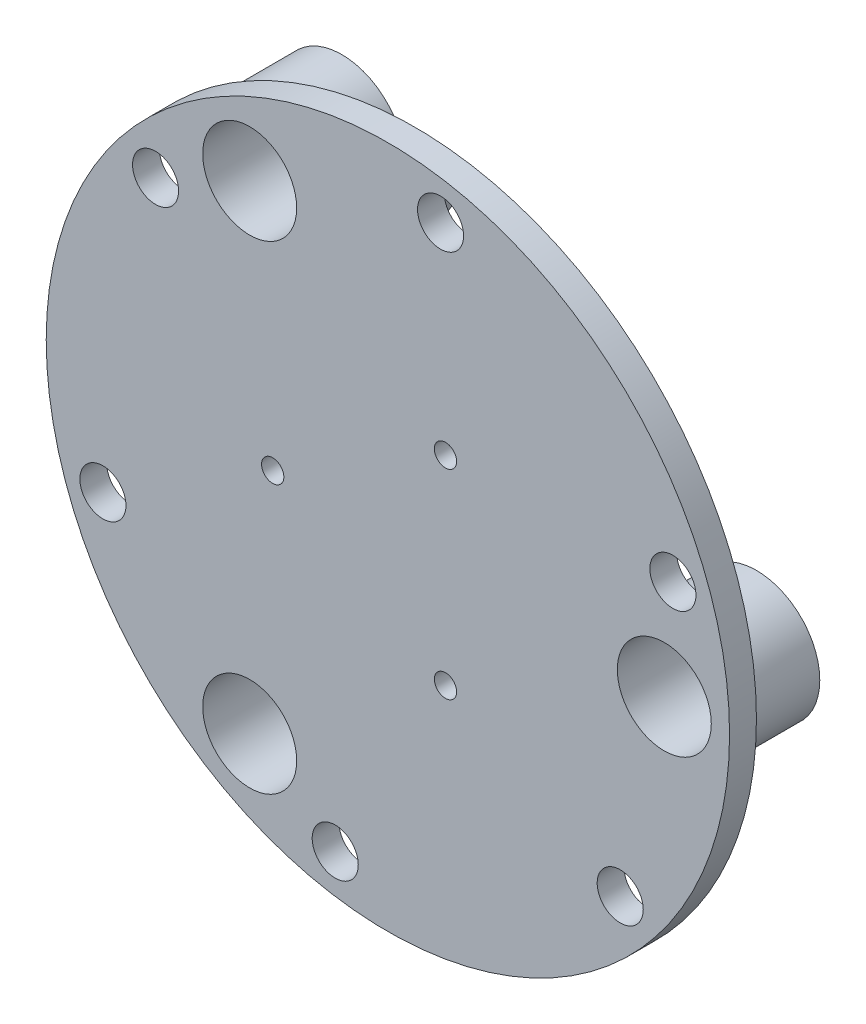
SolidWorks part; units mm, degrees
ref_plane "Front Plane" through (0, 0, 0) normal (0, 0, 1) x (1, 0, 0)
ref_plane "Top Plane" through (0, 0, 0) normal (0, 1, 0) x (1, 0, 0)
ref_plane "Right Plane" through (0, 0, 0) normal (1, 0, 0) x (0, 0, -1)
sketch "S01 - Joining centre of floating Y" plane through (0, 0, 0) normal (0, 0, 1) x (1, 0, 0)
  circle A0 centre (0, 0) radius 9
  dimension "D1" = 18
extrude "01 - Joining centre of floating Y" add sketch "S01 - Joining centre of floating Y" along normal blind 3.5 from offset 33.5
sketch "S02 - Floating spoke 1" plane through (0, 0, 0) normal (0, 0, 1) x (1, 0, 0)
  line L0 (4.65, -8.054) -> (-21.3308, -23.054)
  line L1 (-30.6308, -6.946) -> (-4.65, 8.054)
  arc A0 (-21.3308, -23.054) -> (-30.6308, -6.946) centre (-25.9808, -15) cw
  arc A1 (-4.65, 8.054) -> (4.65, -8.054) centre (0, 0) cw
  dimension "D1" = 9.3
  dimension "D2" = 9.3
  dimension "D3" = 4.65
  dimension "D4" = 4.65
  dimension "D5" = 21.3308
  dimension "D6" = 25.9808
  dimension "D7" = 30.6308
  dimension "D8" = 6.946
extrude "02 - Floating spoke 1" add sketch "S02 - Floating spoke 1" along normal blind 3.5 from offset 33.5
sketch "S03 - Floating spoke 2" plane through (0, 0, 0) normal (0, 0, 1) x (1, 0, 0)
  line L0 (4.65, 8.054) -> (30.6308, -6.946)
  line L1 (21.3308, -23.054) -> (-4.65, -8.054)
  arc A0 (30.6308, -6.946) -> (21.3308, -23.054) centre (25.9808, -15) cw
  arc A1 (-4.65, -8.054) -> (4.65, 8.054) centre (0, 0) cw
  dimension "D1" = 9.3
  dimension "D2" = 9.3
  dimension "D3" = 4.65
  dimension "D4" = 21.3308
  dimension "D5" = 25.9808
  dimension "D6" = 30.6308
  dimension "D7" = 4.65
  dimension "D8" = 6.946
extrude "03 - Floating spoke 2" add sketch "S03 - Floating spoke 2" along normal blind 3.5 from offset 33.5
sketch "S04 - Floating spoke 3" plane through (0, 0, 0) normal (0, 0, 1) x (1, 0, 0)
  line L0 (-9.3, 0) -> (-9.3, 30)
  line L1 (9.3, 30) -> (9.3, 0)
  arc A0 (-9.3, 30) -> (9.3, 30) centre (0, 30) cw
  arc A1 (9.3, 0) -> (-9.3, 0) centre (0, 0) cw
  dimension "D1" = 9.3
  dimension "D2" = 30
extrude "04 - Floating spoke 3" add sketch "S04 - Floating spoke 3" along normal blind 3.5 from offset 33.5
sketch "S05 - Moving tendon tie web 1" plane through (0, 0, 0) normal (0, 0, 1) x (1, 0, 0)
  line L0 (25.2997, -21.2631) -> (6.8189, -19.2535)
  line L1 (8.1811, -6.7273) -> (26.6618, -8.7369)
  arc A0 (6.8189, -19.2535) -> (8.1811, -6.7273) centre (7.5, -12.9904) cw
  arc A1 (26.6618, -8.7369) -> (25.2997, -21.2631) centre (25.9808, -15) cw
  dimension "D1" = 6.3
  dimension "D2" = 6.3
  dimension "D3" = 6.8189
  dimension "D4" = 7.5
  dimension "D5" = 8.1811
  dimension "D6" = 25.2997
  dimension "D7" = 25.9808
  dimension "D8" = 26.6618
  dimension "D9" = 6.7273
  dimension "D10" = 8.7369
extrude "05 - Moving tendon tie web 1" add sketch "S05 - Moving tendon tie web 1" along normal blind 3.5 from offset 33.5
sketch "S06 - Tendon anchor base 1" plane through (0, 0, 0) normal (0, 0, 1) x (1, 0, 0)
  circle A0 centre (7.5, -12.9904) radius 4.2
  dimension "D1" = 8.4
  dimension "D2" = 7.5
  dimension "D3" = 12.9904
extrude "06 - Tendon anchor base 1" add sketch "S06 - Tendon anchor base 1" along normal blind 3.7 from offset 29.8
sketch "S07 - Tendon mouth 1" plane through (0, 0, 0) normal (0, 0, 1) x (1, 0, 0)
  circle A0 centre (7.5, -12.9904) radius 3.15
  dimension "D1" = 6.3
  dimension "D2" = 7.5
  dimension "D3" = 12.9904
extrude "07 - Tendon mouth 1" add sketch "S07 - Tendon mouth 1" along normal blind 1.8 from offset 28
sketch "S08 - Moving tendon tie web 2" plane through (0, 0, 0) normal (0, 0, 1) x (1, 0, 0)
  line L0 (5.7645, 32.5417) -> (13.2645, 15.5321)
  line L1 (1.7355, 10.4487) -> (-5.7645, 27.4583)
  arc A0 (13.2645, 15.5321) -> (1.7355, 10.4487) centre (7.5, 12.9904) cw
  arc A1 (-5.7645, 27.4583) -> (5.7645, 32.5417) centre (0, 30) cw
  dimension "D1" = 6.3
  dimension "D2" = 6.3
  dimension "D3" = 1.7355
  dimension "D4" = 5.7645
  dimension "D5" = 7.5
  dimension "D6" = 13.2645
  dimension "D7" = 5.7645
  dimension "D8" = 10.4487
  dimension "D9" = 27.4583
extrude "08 - Moving tendon tie web 2" add sketch "S08 - Moving tendon tie web 2" along normal blind 3.5 from offset 33.5
sketch "S09 - Tendon anchor base 2" plane through (0, 0, 0) normal (0, 0, 1) x (1, 0, 0)
  circle A0 centre (7.5, 12.9904) radius 4.2
  dimension "D1" = 8.4
  dimension "D2" = 7.5
  dimension "D3" = 12.9904
extrude "09 - Tendon anchor base 2" add sketch "S09 - Tendon anchor base 2" along normal blind 3.7 from offset 29.8
sketch "S10 - Tendon mouth 2" plane through (0, 0, 0) normal (0, 0, 1) x (1, 0, 0)
  circle A0 centre (7.5, 12.9904) radius 3.15
  dimension "D1" = 6.3
  dimension "D2" = 7.5
  dimension "D3" = 12.9904
extrude "10 - Tendon mouth 2" add sketch "S10 - Tendon mouth 2" along normal blind 1.8 from offset 28
sketch "S11 - Moving tendon tie web 3" plane through (0, 0, 0) normal (0, 0, 1) x (1, 0, 0)
  line L0 (-31.0642, -11.2786) -> (-20.0835, 3.7214)
  line L1 (-9.9165, -3.7214) -> (-20.8973, -18.7214)
  arc A0 (-20.0835, 3.7214) -> (-9.9165, -3.7214) centre (-15, 0) cw
  arc A1 (-20.8973, -18.7214) -> (-31.0642, -11.2786) centre (-25.9808, -15) cw
  dimension "D1" = 6.3
  dimension "D2" = 6.3
  dimension "D3" = 9.9165
  dimension "D4" = 15
  dimension "D5" = 20.0835
  dimension "D6" = 20.8973
  dimension "D7" = 25.9808
  dimension "D8" = 31.0642
  dimension "D9" = 11.2786
extrude "11 - Moving tendon tie web 3" add sketch "S11 - Moving tendon tie web 3" along normal blind 3.5 from offset 33.5
sketch "S12 - Tendon anchor base 3" plane through (0, 0, 0) normal (0, 0, 1) x (1, 0, 0)
  circle A0 centre (-15, 0) radius 4.2
  dimension "D1" = 8.4
  dimension "D2" = 15
extrude "12 - Tendon anchor base 3" add sketch "S12 - Tendon anchor base 3" along normal blind 3.7 from offset 29.8
sketch "S13 - Tendon mouth 3" plane through (0, 0, 0) normal (0, 0, 1) x (1, 0, 0)
  circle A0 centre (-15, 0) radius 3.15
  dimension "D1" = 6.3
  dimension "D2" = 15
extrude "13 - Tendon mouth 3" add sketch "S13 - Tendon mouth 3" along normal blind 1.8 from offset 28
sketch "S14 - Joined drive hoop" plane through (0, 0, 0) normal (0, 0, 1) x (1, 0, 0)
  circle A0 centre (0, 0) radius 44.5
  dimension "D2" = 89
extrude "14 - Joined drive hoop" add sketch "S14 - Joined drive hoop" along normal blind 3.5 from offset 33.5
sketch "S15 - Sliding guide barrel 1" plane through (0, 0, 0) normal (0, 0, 1) x (1, 0, 0)
  circle A0 centre (36, 0) radius 8.25
  dimension "D1" = 16.5
  dimension "D2" = 36
extrude "15 - Sliding guide barrel 1" add sketch "S15 - Sliding guide barrel 1" along normal blind 12 from offset 25
sketch "S16 - Sliding guide barrel 2" plane through (0, 0, 0) normal (0, 0, 1) x (1, 0, 0)
  circle A0 centre (-18, 31.1769) radius 8.25
  dimension "D1" = 16.5
  dimension "D2" = 18
  dimension "D3" = 31.1769
extrude "16 - Sliding guide barrel 2" add sketch "S16 - Sliding guide barrel 2" along normal blind 12 from offset 25
sketch "S17 - Sliding guide barrel 3" plane through (0, 0, 0) normal (0, 0, 1) x (1, 0, 0)
  circle A0 centre (-18, -31.1769) radius 8.25
  dimension "D1" = 16.5
  dimension "D2" = 18
  dimension "D3" = 31.1769
extrude "17 - Sliding guide barrel 3" add sketch "S17 - Sliding guide barrel 3" along normal blind 12 from offset 25
sketch "S18 - Guide bushing seats" plane through (0, 0, 0) normal (0, 0, 1) x (1, 0, 0)
  circle A0 centre (36, 0) radius 6.12
  circle A1 centre (-18, 31.1769) radius 6.12
  circle A2 centre (-18, -31.1769) radius 6.12
  dimension "D1" = 12.24
  dimension "D2" = 12.24
  dimension "D3" = 12.24
  dimension "D4" = 36
  dimension "D5" = 18
  dimension "D6" = 31.1769
  dimension "D7" = 31.1769
extrude "18 - Guide bushing seats" cut sketch "S18 - Guide bushing seats" along normal blind 14 from offset 24
sketch "S19 - Through tendon tie eyes" plane through (0, 0, 0) normal (0, 0, 1) x (1, 0, 0)
  circle A0 centre (7.5, -12.9904) radius 1.45
  circle A1 centre (7.5, 12.9904) radius 1.45
  circle A2 centre (-15, 0) radius 1.45
  dimension "D1" = 2.9
  dimension "D2" = 2.9
  dimension "D3" = 2.9
  dimension "D4" = 7.5
  dimension "D5" = 15
  dimension "D6" = 12.9904
  dimension "D7" = 12.9904
extrude "19 - Through tendon tie eyes" cut sketch "S19 - Through tendon tie eyes" along normal blind 10 from offset 27.8
sketch3d "Plane points - Integral B1 fork cheek L"
  point P0 (-25.9808, -15, 28)
  point P1 (-8.5941, -10.3413, 28)
  point P2 (-25.9808, -15, 10)
ref_plane "Drilling plane - Integral B1 fork cheek L" through (2.0096, -7.5, 0) normal (-0.2588, 0.9659, 0) x (0.9659, 0.2588, 0)
sketch "S20 - Integral B1 fork cheek L" plane through (2.0096, -7.5, 0) normal (-0.2588, 0.9659, 0) x (0.9659, 0.2588, 0)
  line L0 (-35.0778, -34.5) -> (-22.8778, -34.5)
  line L1 (-22.8778, -34.5) -> (-24.0278, -28)
  line L2 (-33.9278, -28) -> (-35.0778, -34.5)
  arc A0 (-24.0278, -28) -> (-33.9278, -28) centre (-28.9778, -28) ccw
  dimension "D1" = 4.95
  dimension "D2" = 22.8778
  dimension "D3" = 28.9778
  dimension "D4" = 35.0778
  dimension "D5" = 28
  dimension "D6" = 34.5
extrude "20 - Integral B1 fork cheek L" add sketch "S20 - Integral B1 fork cheek L" along normal blind 3.6 from offset 7.2 offset against normal yes
sketch3d "Plane points - Integral B1 fork cheek R"
  point P0 (-25.9808, -15, 28)
  point P1 (-8.5941, -10.3413, 28)
  point P2 (-25.9808, -15, 10)
ref_plane "Drilling plane - Integral B1 fork cheek R" through (2.0096, -7.5, 0) normal (-0.2588, 0.9659, 0) x (0.9659, 0.2588, 0)
sketch "S21 - Integral B1 fork cheek R" plane through (2.0096, -7.5, 0) normal (-0.2588, 0.9659, 0) x (0.9659, 0.2588, 0)
  line L0 (-35.0778, -34.5) -> (-22.8778, -34.5)
  line L1 (-22.8778, -34.5) -> (-24.0278, -28)
  line L2 (-33.9278, -28) -> (-35.0778, -34.5)
  arc A0 (-24.0278, -28) -> (-33.9278, -28) centre (-28.9778, -28) ccw
  dimension "D1" = 4.95
  dimension "D2" = 22.8778
  dimension "D3" = 28.9778
  dimension "D4" = 35.0778
  dimension "D5" = 28
  dimension "D6" = 34.5
extrude "21 - Integral B1 fork cheek R" add sketch "S21 - Integral B1 fork cheek R" along normal blind 3.6 from offset 3.6
sketch3d "Plane points - B1 pivot through both cheeks"
  point P0 (-25.9808, -15, 28)
  point P1 (-8.5941, -10.3413, 28)
  point P2 (-25.9808, -15, 10)
ref_plane "Drilling plane - B1 pivot through both cheeks" through (2.0096, -7.5, 0) normal (-0.2588, 0.9659, 0) x (0.9659, 0.2588, 0)
sketch "S22 - B1 pivot through both cheeks" plane through (2.0096, -7.5, 0) normal (-0.2588, 0.9659, 0) x (0.9659, 0.2588, 0)
  circle A0 centre (-28.9778, -28) radius 1.65
  dimension "D1" = 3.3
  dimension "D2" = 28.9778
  dimension "D3" = 28
extrude "22 - B1 pivot through both cheeks" cut sketch "S22 - B1 pivot through both cheeks" along normal blind 15 from offset 7.5 offset against normal yes
sketch3d "Plane points - B1 recessed pivot screw head"
  point P0 (-25.9808, -15, 28)
  point P1 (-8.5941, -10.3413, 28)
  point P2 (-25.9808, -15, 10)
ref_plane "Drilling plane - B1 recessed pivot screw head" through (2.0096, -7.5, 0) normal (-0.2588, 0.9659, 0) x (0.9659, 0.2588, 0)
sketch "S23 - B1 recessed pivot screw head" plane through (2.0096, -7.5, 0) normal (-0.2588, 0.9659, 0) x (0.9659, 0.2588, 0)
  circle A0 centre (-28.9778, -28) radius 2.7
  dimension "D1" = 5.4
  dimension "D2" = 28.9778
  dimension "D3" = 28
extrude "23 - B1 recessed pivot screw head" cut sketch "S23 - B1 recessed pivot screw head" along normal blind 1.5 from offset 7.3 offset against normal yes
sketch3d "Plane points - Integral B2 fork cheek L"
  point P0 (25.9808, -15, 28)
  point P1 (13.2528, -2.2721, 28)
  point P2 (25.9808, -15, 10)
ref_plane "Drilling plane - Integral B2 fork cheek L" through (5.4904, 5.4904, 0) normal (-0.7071, -0.7071, 0) x (0, 0, 1)
sketch "S24 - Integral B2 fork cheek L" plane through (5.4904, 5.4904, 0) normal (-0.7071, -0.7071, 0) x (0, 0, 1)
  line L0 (34.5, -35.0778) -> (34.5, -22.8778)
  line L1 (34.5, -22.8778) -> (28, -24.0278)
  line L2 (28, -33.9278) -> (34.5, -35.0778)
  arc A0 (28, -24.0278) -> (28, -33.9278) centre (28, -28.9778) ccw
  dimension "D1" = 4.95
  dimension "D2" = 28
  dimension "D3" = 34.5
  dimension "D4" = 22.8778
  dimension "D5" = 28.9778
  dimension "D6" = 35.0778
extrude "24 - Integral B2 fork cheek L" add sketch "S24 - Integral B2 fork cheek L" along normal blind 3.6 from offset 7.2 offset against normal yes
sketch3d "Plane points - Integral B2 fork cheek R"
  point P0 (25.9808, -15, 28)
  point P1 (13.2528, -2.2721, 28)
  point P2 (25.9808, -15, 10)
ref_plane "Drilling plane - Integral B2 fork cheek R" through (5.4904, 5.4904, 0) normal (-0.7071, -0.7071, 0) x (0, 0, 1)
sketch "S25 - Integral B2 fork cheek R" plane through (5.4904, 5.4904, 0) normal (-0.7071, -0.7071, 0) x (0, 0, 1)
  line L0 (34.5, -35.0778) -> (34.5, -22.8778)
  line L1 (34.5, -22.8778) -> (28, -24.0278)
  line L2 (28, -33.9278) -> (34.5, -35.0778)
  arc A0 (28, -24.0278) -> (28, -33.9278) centre (28, -28.9778) ccw
  dimension "D1" = 4.95
  dimension "D2" = 28
  dimension "D3" = 34.5
  dimension "D4" = 22.8778
  dimension "D5" = 28.9778
  dimension "D6" = 35.0778
extrude "25 - Integral B2 fork cheek R" add sketch "S25 - Integral B2 fork cheek R" along normal blind 3.6 from offset 3.6
sketch3d "Plane points - B2 pivot through both cheeks"
  point P0 (25.9808, -15, 28)
  point P1 (13.2528, -2.2721, 28)
  point P2 (25.9808, -15, 10)
ref_plane "Drilling plane - B2 pivot through both cheeks" through (5.4904, 5.4904, 0) normal (-0.7071, -0.7071, 0) x (0, 0, 1)
sketch "S26 - B2 pivot through both cheeks" plane through (5.4904, 5.4904, 0) normal (-0.7071, -0.7071, 0) x (0, 0, 1)
  circle A0 centre (28, -28.9778) radius 2.6
  dimension "D1" = 5.2
  dimension "D2" = 28
  dimension "D3" = 28.9778
extrude "26 - B2 pivot through both cheeks" cut sketch "S26 - B2 pivot through both cheeks" along normal blind 15 from offset 7.5 offset against normal yes
sketch3d "Plane points - B2 recessed pivot screw head"
  point P0 (25.9808, -15, 28)
  point P1 (13.2528, -2.2721, 28)
  point P2 (25.9808, -15, 10)
ref_plane "Drilling plane - B2 recessed pivot screw head" through (5.4904, 5.4904, 0) normal (-0.7071, -0.7071, 0) x (0, 0, 1)
sketch "S27 - B2 recessed pivot screw head" plane through (5.4904, 5.4904, 0) normal (-0.7071, -0.7071, 0) x (0, 0, 1)
  circle A0 centre (28, -28.9778) radius 2.7
  dimension "D1" = 5.4
  dimension "D2" = 28
  dimension "D3" = 28.9778
extrude "27 - B2 recessed pivot screw head" cut sketch "S27 - B2 recessed pivot screw head" along normal blind 1.5 from offset 7.3 offset against normal yes
sketch3d "Plane points - Integral B3 fork cheek L"
  point P0 (0, 30, 28)
  point P1 (-4.6587, 12.6133, 28)
  point P2 (0, 30, 10)
ref_plane "Drilling plane - Integral B3 fork cheek L" through (-7.5, 2.0096, 0) normal (0.9659, -0.2588, 0) x (0, 0, -1)
sketch "S28 - Integral B3 fork cheek L" plane through (-7.5, 2.0096, 0) normal (0.9659, -0.2588, 0) x (0, 0, -1)
  line L0 (-34.5, 35.0778) -> (-34.5, 22.8778)
  line L1 (-34.5, 22.8778) -> (-28, 24.0278)
  line L2 (-28, 33.9278) -> (-34.5, 35.0778)
  arc A0 (-28, 24.0278) -> (-28, 33.9278) centre (-28, 28.9778) ccw
  dimension "D1" = 4.95
  dimension "D2" = 28
  dimension "D3" = 34.5
  dimension "D4" = 22.8778
  dimension "D5" = 28.9778
  dimension "D6" = 35.0778
extrude "28 - Integral B3 fork cheek L" add sketch "S28 - Integral B3 fork cheek L" along normal blind 3.6 from offset 7.2 offset against normal yes
sketch3d "Plane points - Integral B3 fork cheek R"
  point P0 (0, 30, 28)
  point P1 (-4.6587, 12.6133, 28)
  point P2 (0, 30, 10)
ref_plane "Drilling plane - Integral B3 fork cheek R" through (-7.5, 2.0096, 0) normal (0.9659, -0.2588, 0) x (0, 0, -1)
sketch "S29 - Integral B3 fork cheek R" plane through (-7.5, 2.0096, 0) normal (0.9659, -0.2588, 0) x (0, 0, -1)
  line L0 (-34.5, 35.0778) -> (-34.5, 22.8778)
  line L1 (-34.5, 22.8778) -> (-28, 24.0278)
  line L2 (-28, 33.9278) -> (-34.5, 35.0778)
  arc A0 (-28, 24.0278) -> (-28, 33.9278) centre (-28, 28.9778) ccw
  dimension "D1" = 4.95
  dimension "D2" = 28
  dimension "D3" = 34.5
  dimension "D4" = 22.8778
  dimension "D5" = 28.9778
  dimension "D6" = 35.0778
extrude "29 - Integral B3 fork cheek R" add sketch "S29 - Integral B3 fork cheek R" along normal blind 3.6 from offset 3.6
sketch3d "Plane points - B3 pivot through both cheeks"
  point P0 (0, 30, 28)
  point P1 (-4.6587, 12.6133, 28)
  point P2 (0, 30, 10)
ref_plane "Drilling plane - B3 pivot through both cheeks" through (-7.5, 2.0096, 0) normal (0.9659, -0.2588, 0) x (0, 0, -1)
sketch "S30 - B3 pivot through both cheeks" plane through (-7.5, 2.0096, 0) normal (0.9659, -0.2588, 0) x (0, 0, -1)
  circle A0 centre (-28, 28.9778) radius 2.6
  dimension "D1" = 5.2
  dimension "D2" = 28
  dimension "D3" = 28.9778
extrude "30 - B3 pivot through both cheeks" cut sketch "S30 - B3 pivot through both cheeks" along normal blind 15 from offset 7.5 offset against normal yes
sketch3d "Plane points - B3 recessed pivot screw head"
  point P0 (0, 30, 28)
  point P1 (-4.6587, 12.6133, 28)
  point P2 (0, 30, 10)
ref_plane "Drilling plane - B3 recessed pivot screw head" through (-7.5, 2.0096, 0) normal (0.9659, -0.2588, 0) x (0, 0, -1)
sketch "S31 - B3 recessed pivot screw head" plane through (-7.5, 2.0096, 0) normal (0.9659, -0.2588, 0) x (0, 0, -1)
  circle A0 centre (-28, 28.9778) radius 2.7
  dimension "D1" = 5.4
  dimension "D2" = 28
  dimension "D3" = 28.9778
extrude "31 - B3 recessed pivot screw head" cut sketch "S31 - B3 recessed pivot screw head" along normal blind 1.5 from offset 7.3 offset against normal yes
sketch "Sketch1" plane through (0.1461, -0.5453, 0) normal (-0.2588, 0.9659, 0) x (0.9659, 0.2588, 0)
  circle A0 centre (-28.9778, -28) radius 2.6
  dimension "D1" = 5.2
extrude "Cut-Extrude1" cut sketch "Sketch1" against normal blind 16 and the other way through all
sketch "Sketch2" plane through (0, 0, 33.5) normal (0, 0, -1) x (-1, 0, 0)
other "Fork inner faces - 8.40 mm lug clearance" flip direction yes face at (-27.5604, -19.1503, 28) face at (-29.4239, -12.1956, 28) face at (30.3648, -14.2929, 28) face at (25.2737, -19.3841, 28) face at (-2.8044, 33.4432, 28) face at (4.1503, 31.5797, 28) offset 0.6 parameters "D1"=0.6
ref_plane "Guide saddle feet" through (0, 0, 25.5) normal (0, 0, 1) x (1, 0, 0)
ref_plane "Guide saddle roots" through (0, 0, 33.6) normal (0, 0, 1) x (1, 0, 0)
sketch "Barrel 1 saddle foot" plane through (0, 0, 25.5) normal (0, 0, 1) x (1, 0, 0)
  line L0 (36, -8) -> (31, -8)
  line L1 (31, -8) -> (27, -3)
  line L2 (27, 3) -> (31, 8)
  line L3 (31, 8) -> (36, 8)
  line L4 (36, 8) -> (36, 7)
  line L5 (36, -7) -> (36, -8)
  arc A0 (27, -3) -> (27, 3) centre (27, 0) cw
  arc A1 (36, 7) -> (36, -7) centre (36, 0) ccw
sketch "Barrel 1 saddle root" plane through (0, 0, 33.6) normal (0, 0, 1) x (1, 0, 0)
  line L0 (36, -8) -> (31, -8)
  line L1 (31, -8) -> (20, -4)
  line L2 (20, 4) -> (31, 8)
  line L3 (31, 8) -> (36, 8)
  line L4 (36, 8) -> (36, 7)
  line L5 (36, -7) -> (36, -8)
  arc A0 (20, -4) -> (20, 4) centre (20, 0) cw
  arc A1 (36, 7) -> (36, -7) centre (36, 0) ccw
loft "Guide barrel 1 - tapered wraparound saddle" [suppressed] add profiles "Barrel 1 saddle foot", "Barrel 1 saddle root"
sketch "Barrel 2 saddle foot" plane through (0, 0, 25.5) normal (0, 0, 1) x (1, 0, 0)
  line L0 (-11.0718, 35.1769) -> (-8.5718, 30.8468)
  line L1 (-8.5718, 30.8468) -> (-10.9019, 24.8827)
  line L2 (-16.0981, 21.8827) -> (-22.4282, 22.8468)
  line L3 (-22.4282, 22.8468) -> (-24.9282, 27.1769)
  line L4 (-24.9282, 27.1769) -> (-24.0622, 27.6769)
  line L5 (-11.9378, 34.6769) -> (-11.0718, 35.1769)
  arc A0 (-10.9019, 24.8827) -> (-16.0981, 21.8827) centre (-13.5, 23.3827) cw
  arc A1 (-24.0622, 27.6769) -> (-11.9378, 34.6769) centre (-18, 31.1769) ccw
sketch "Barrel 2 saddle root" plane through (0, 0, 33.6) normal (0, 0, 1) x (1, 0, 0)
  line L0 (-11.0718, 35.1769) -> (-8.5718, 30.8468)
  line L1 (-8.5718, 30.8468) -> (-6.5359, 19.3205)
  line L2 (-13.4641, 15.3205) -> (-22.4282, 22.8468)
  line L3 (-22.4282, 22.8468) -> (-24.9282, 27.1769)
  line L4 (-24.9282, 27.1769) -> (-24.0622, 27.6769)
  line L5 (-11.9378, 34.6769) -> (-11.0718, 35.1769)
  arc A0 (-6.5359, 19.3205) -> (-13.4641, 15.3205) centre (-10, 17.3205) cw
  arc A1 (-24.0622, 27.6769) -> (-11.9378, 34.6769) centre (-18, 31.1769) ccw
loft "Guide barrel 2 - tapered wraparound saddle" [suppressed] add profiles "Barrel 2 saddle foot", "Barrel 2 saddle root"
sketch "Barrel 3 saddle foot" plane through (0, 0, 25.5) normal (0, 0, 1) x (1, 0, 0)
  line L0 (-24.9282, -27.1769) -> (-22.4282, -22.8468)
  line L1 (-22.4282, -22.8468) -> (-16.0981, -21.8827)
  line L2 (-10.9019, -24.8827) -> (-8.5718, -30.8468)
  line L3 (-8.5718, -30.8468) -> (-11.0718, -35.1769)
  line L4 (-11.0718, -35.1769) -> (-11.9378, -34.6769)
  line L5 (-24.0622, -27.6769) -> (-24.9282, -27.1769)
  arc A0 (-16.0981, -21.8827) -> (-10.9019, -24.8827) centre (-13.5, -23.3827) cw
  arc A1 (-11.9378, -34.6769) -> (-24.0622, -27.6769) centre (-18, -31.1769) ccw
sketch "Barrel 3 saddle root" plane through (0, 0, 33.6) normal (0, 0, 1) x (1, 0, 0)
  line L0 (-24.9282, -27.1769) -> (-22.4282, -22.8468)
  line L1 (-22.4282, -22.8468) -> (-13.4641, -15.3205)
  line L2 (-6.5359, -19.3205) -> (-8.5718, -30.8468)
  line L3 (-8.5718, -30.8468) -> (-11.0718, -35.1769)
  line L4 (-11.0718, -35.1769) -> (-11.9378, -34.6769)
  line L5 (-24.0622, -27.6769) -> (-24.9282, -27.1769)
  arc A0 (-13.4641, -15.3205) -> (-6.5359, -19.3205) centre (-10, -17.3205) cw
  arc A1 (-11.9378, -34.6769) -> (-24.0622, -27.6769) centre (-18, -31.1769) ccw
loft "Guide barrel 3 - tapered wraparound saddle" [suppressed] add profiles "Barrel 3 saddle foot", "Barrel 3 saddle root"
sketch "Tangent R6.5 transitions at guide stations" plane through (0, 0, 0) normal (0, 0, 1) x (1, 0, 0)
  line L0 (39.3501, -7.5392) -> (35.4, -7.5)
  line L1 (35.4, -7.5) -> (35.8006, -11.4924)
  line L2 (39.3501, 7.5392) -> (35.4, 7.5)
  line L3 (35.4, 7.5) -> (35.8006, 11.4924)
  line L4 (-13.1459, 37.8478) -> (-11.2048, 34.4073)
  line L5 (-11.2048, 34.4073) -> (-7.9476, 36.7505)
  line L6 (-26.2042, 30.3086) -> (-24.1952, 26.9073)
  line L7 (-24.1952, 26.9073) -> (-27.853, 25.258)
  line L8 (-26.2042, -30.3086) -> (-24.1952, -26.9073)
  line L9 (-24.1952, -26.9073) -> (-27.853, -25.258)
  line L10 (-13.1459, -37.8478) -> (-11.2048, -34.4073)
  line L11 (-11.2048, -34.4073) -> (-7.9476, -36.7505)
  arc A0 (35.8006, -11.4924) -> (39.3501, -7.5392) centre (41.9895, -13.4792) cw
  arc A1 (35.8006, 11.4924) -> (39.3501, 7.5392) centre (41.9895, 13.4792) ccw
  arc A2 (-7.9476, 36.7505) -> (-13.1459, 37.8478) centre (-9.3215, 43.1036) cw
  arc A3 (-27.853, 25.258) -> (-26.2042, 30.3086) centre (-32.6681, 29.6244) ccw
  arc A4 (-27.853, -25.258) -> (-26.2042, -30.3086) centre (-32.6681, -29.6244) cw
  arc A5 (-7.9476, -36.7505) -> (-13.1459, -37.8478) centre (-9.3215, -43.1036) ccw
extrude "Continuous deck rim around bearing housings" [suppressed] add sketch "Tangent R6.5 transitions at guide stations" along normal blind 3.5 from offset 33.5
sketch3d "Guide 1 clockwise anchor section"
  line L0 (11.4747, -15.0801, 33.56) -> (8.53, -8.6195, 33.56)
  line L1 (8.53, -8.6195, 33.56) -> (8.9447, -9.5295, 32.56)
  line L2 (8.9447, -9.5295, 32.56) -> (9.1313, -9.939, 30.55)
  line L3 (9.1313, -9.939, 30.55) -> (9.318, -10.3484, 30.1)
  line L4 (9.318, -10.3484, 30.1) -> (10.6867, -13.3512, 30.1)
  line L5 (10.6867, -13.3512, 30.1) -> (10.8733, -13.7607, 30.55)
  line L6 (10.8733, -13.7607, 30.55) -> (11.0599, -14.1702, 32.56)
  line L7 (11.0599, -14.1702, 32.56) -> (11.4747, -15.0801, 33.56)
sketch3d "Guide 1 clockwise web section"
  line L0 (19.1463, -10.8141, 33.56) -> (16.7822, -5.6274, 33.56)
  line L1 (16.7822, -5.6274, 33.56) -> (17.197, -6.5374, 32.56)
  line L2 (17.197, -6.5374, 32.56) -> (17.3836, -6.9468, 30.45)
  line L3 (17.3836, -6.9468, 30.45) -> (17.5702, -7.3563, 30)
  line L4 (17.5702, -7.3563, 30) -> (18.3583, -9.0852, 30)
  line L5 (18.3583, -9.0852, 30) -> (18.5449, -9.4947, 30.45)
  line L6 (18.5449, -9.4947, 30.45) -> (18.7315, -9.9041, 32.56)
  line L7 (18.7315, -9.9041, 32.56) -> (19.1463, -10.8141, 33.56)
sketch3d "Guide 1 clockwise haunch section"
  line L0 (26.5692, -7.7604, 33.56) -> (23.9563, -2.0278, 33.56)
  line L1 (23.9563, -2.0278, 33.56) -> (24.3711, -2.9377, 32.56)
  line L2 (24.3711, -2.9377, 32.56) -> (24.5577, -3.3472, 27.45)
  line L3 (24.5577, -3.3472, 27.45) -> (24.7443, -3.7566, 27)
  line L4 (24.7443, -3.7566, 27) -> (25.7812, -6.0315, 27)
  line L5 (25.7812, -6.0315, 27) -> (25.9678, -6.441, 27.45)
  line L6 (25.9678, -6.441, 27.45) -> (26.1545, -6.8504, 32.56)
  line L7 (26.1545, -6.8504, 32.56) -> (26.5692, -7.7604, 33.56)
sketch3d "Guide 1 clockwise housing section"
  line L0 (31.8441, -6.6748, 33.56) -> (28.2358, 1.2416, 33.56)
  line L1 (28.2358, 1.2416, 33.56) -> (28.6505, 0.3317, 32.56)
  line L2 (28.6505, 0.3317, 32.56) -> (28.8371, -0.0778, 25.9)
  line L3 (28.8371, -0.0778, 25.9) -> (29.0238, -0.4873, 25.45)
  line L4 (29.0238, -0.4873, 25.45) -> (31.0561, -4.946, 25.45)
  line L5 (31.0561, -4.946, 25.45) -> (31.2427, -5.3554, 25.9)
  line L6 (31.2427, -5.3554, 25.9) -> (31.4293, -5.7649, 32.56)
  line L7 (31.4293, -5.7649, 32.56) -> (31.8441, -6.6748, 33.56)
loft "Guide 1 clockwise bearing-to-anchor rib" [suppressed] add profiles "Guide 1 clockwise anchor section", "Guide 1 clockwise web section", "Guide 1 clockwise haunch section", "Guide 1 clockwise housing section"
sketch3d "Guide 1 counterclockwise anchor section"
  line L0 (8.53, 8.6195, 33.56) -> (11.4747, 15.0801, 33.56)
  line L1 (11.4747, 15.0801, 33.56) -> (11.0599, 14.1702, 32.56)
  line L2 (11.0599, 14.1702, 32.56) -> (10.8733, 13.7607, 30.55)
  line L3 (10.8733, 13.7607, 30.55) -> (10.6867, 13.3512, 30.1)
  line L4 (10.6867, 13.3512, 30.1) -> (9.318, 10.3484, 30.1)
  line L5 (9.318, 10.3484, 30.1) -> (9.1313, 9.939, 30.55)
  line L6 (9.1313, 9.939, 30.55) -> (8.9447, 9.5295, 32.56)
  line L7 (8.9447, 9.5295, 32.56) -> (8.53, 8.6195, 33.56)
sketch3d "Guide 1 counterclockwise web section"
  line L0 (16.7822, 5.6274, 33.56) -> (19.1463, 10.8141, 33.56)
  line L1 (19.1463, 10.8141, 33.56) -> (18.7315, 9.9041, 32.56)
  line L2 (18.7315, 9.9041, 32.56) -> (18.5449, 9.4947, 30.45)
  line L3 (18.5449, 9.4947, 30.45) -> (18.3583, 9.0852, 30)
  line L4 (18.3583, 9.0852, 30) -> (17.5702, 7.3563, 30)
  line L5 (17.5702, 7.3563, 30) -> (17.3836, 6.9468, 30.45)
  line L6 (17.3836, 6.9468, 30.45) -> (17.197, 6.5374, 32.56)
  line L7 (17.197, 6.5374, 32.56) -> (16.7822, 5.6274, 33.56)
sketch3d "Guide 1 counterclockwise haunch section"
  line L0 (23.9563, 2.0278, 33.56) -> (26.5692, 7.7604, 33.56)
  line L1 (26.5692, 7.7604, 33.56) -> (26.1545, 6.8504, 32.56)
  line L2 (26.1545, 6.8504, 32.56) -> (25.9678, 6.441, 27.45)
  line L3 (25.9678, 6.441, 27.45) -> (25.7812, 6.0315, 27)
  line L4 (25.7812, 6.0315, 27) -> (24.7443, 3.7566, 27)
  line L5 (24.7443, 3.7566, 27) -> (24.5577, 3.3472, 27.45)
  line L6 (24.5577, 3.3472, 27.45) -> (24.3711, 2.9377, 32.56)
  line L7 (24.3711, 2.9377, 32.56) -> (23.9563, 2.0278, 33.56)
sketch3d "Guide 1 counterclockwise housing section"
  line L0 (28.2358, -1.2416, 33.56) -> (31.8441, 6.6748, 33.56)
  line L1 (31.8441, 6.6748, 33.56) -> (31.4293, 5.7649, 32.56)
  line L2 (31.4293, 5.7649, 32.56) -> (31.2427, 5.3554, 25.9)
  line L3 (31.2427, 5.3554, 25.9) -> (31.0561, 4.946, 25.45)
  line L4 (31.0561, 4.946, 25.45) -> (29.0238, 0.4873, 25.45)
  line L5 (29.0238, 0.4873, 25.45) -> (28.8371, 0.0778, 25.9)
  line L6 (28.8371, 0.0778, 25.9) -> (28.6505, -0.3317, 32.56)
  line L7 (28.6505, -0.3317, 32.56) -> (28.2358, -1.2416, 33.56)
loft "Guide 1 counterclockwise bearing-to-anchor rib" [suppressed] add profiles "Guide 1 counterclockwise anchor section", "Guide 1 counterclockwise web section", "Guide 1 counterclockwise haunch section", "Guide 1 counterclockwise housing section"
sketch3d "Guide 2 clockwise anchor section"
  line L0 (7.3224, 17.4774, 33.56) -> (3.1998, 11.6969, 33.56)
  line L1 (3.1998, 11.6969, 33.56) -> (3.7804, 12.5111, 32.56)
  line L2 (3.7804, 12.5111, 32.56) -> (4.0417, 12.8775, 30.55)
  line L3 (4.0417, 12.8775, 30.55) -> (4.303, 13.2438, 30.1)
  line L4 (4.303, 13.2438, 30.1) -> (6.2192, 15.9305, 30.1)
  line L5 (6.2192, 15.9305, 30.1) -> (6.4804, 16.2969, 30.55)
  line L6 (6.4804, 16.2969, 30.55) -> (6.7417, 16.6633, 32.56)
  line L7 (6.7417, 16.6633, 32.56) -> (7.3224, 17.4774, 33.56)
sketch3d "Guide 2 clockwise web section"
  line L0 (-0.2079, 21.9882, 33.56) -> (-3.5176, 17.3475, 33.56)
  line L1 (-3.5176, 17.3475, 33.56) -> (-2.937, 18.1617, 32.56)
  line L2 (-2.937, 18.1617, 32.56) -> (-2.6757, 18.5281, 30.45)
  line L3 (-2.6757, 18.5281, 30.45) -> (-2.4144, 18.8944, 30)
  line L4 (-2.4144, 18.8944, 30) -> (-1.3111, 20.4413, 30)
  line L5 (-1.3111, 20.4413, 30) -> (-1.0498, 20.8077, 30.45)
  line L6 (-1.0498, 20.8077, 30.45) -> (-0.7885, 21.1741, 32.56)
  line L7 (-0.7885, 21.1741, 32.56) -> (-0.2079, 21.9882, 33.56)
sketch3d "Guide 2 clockwise haunch section"
  line L0 (-6.564, 26.8898, 33.56) -> (-10.2221, 21.7606, 33.56)
  line L1 (-10.2221, 21.7606, 33.56) -> (-9.6414, 22.5748, 32.56)
  line L2 (-9.6414, 22.5748, 32.56) -> (-9.3801, 22.9412, 27.45)
  line L3 (-9.3801, 22.9412, 27.45) -> (-9.1188, 23.3075, 27)
  line L4 (-9.1188, 23.3075, 27) -> (-7.6672, 25.3429, 27)
  line L5 (-7.6672, 25.3429, 27) -> (-7.4059, 25.7093, 27.45)
  line L6 (-7.4059, 25.7093, 27.45) -> (-7.1446, 26.0757, 32.56)
  line L7 (-7.1446, 26.0757, 32.56) -> (-6.564, 26.8898, 33.56)
sketch3d "Guide 2 clockwise housing section"
  line L0 (-10.1415, 30.9152, 33.56) -> (-15.1931, 23.8321, 33.56)
  line L1 (-15.1931, 23.8321, 33.56) -> (-14.6125, 24.6462, 32.56)
  line L2 (-14.6125, 24.6462, 32.56) -> (-14.3512, 25.0126, 25.9)
  line L3 (-14.3512, 25.0126, 25.9) -> (-14.0899, 25.379, 25.45)
  line L4 (-14.0899, 25.379, 25.45) -> (-11.2447, 29.3683, 25.45)
  line L5 (-11.2447, 29.3683, 25.45) -> (-10.9834, 29.7347, 25.9)
  line L6 (-10.9834, 29.7347, 25.9) -> (-10.7221, 30.1011, 32.56)
  line L7 (-10.7221, 30.1011, 32.56) -> (-10.1415, 30.9152, 33.56)
loft "Guide 2 clockwise bearing-to-anchor rib" [suppressed] add profiles "Guide 2 clockwise anchor section", "Guide 2 clockwise web section", "Guide 2 clockwise haunch section", "Guide 2 clockwise housing section"
sketch3d "Guide 2 counterclockwise anchor section"
  line L0 (-11.7297, 3.0774, 33.56) -> (-18.7971, 2.3973, 33.56)
  line L1 (-18.7971, 2.3973, 33.56) -> (-17.8017, 2.4931, 32.56)
  line L2 (-17.8017, 2.4931, 32.56) -> (-17.3537, 2.5362, 30.55)
  line L3 (-17.3537, 2.5362, 30.55) -> (-16.9058, 2.5793, 30.1)
  line L4 (-16.9058, 2.5793, 30.1) -> (-13.621, 2.8954, 30.1)
  line L5 (-13.621, 2.8954, 30.1) -> (-13.1731, 2.9385, 30.55)
  line L6 (-13.1731, 2.9385, 30.55) -> (-12.7251, 2.9816, 32.56)
  line L7 (-12.7251, 2.9816, 32.56) -> (-11.7297, 3.0774, 33.56)
sketch3d "Guide 2 counterclockwise web section"
  line L0 (-13.2646, 11.7201, 33.56) -> (-18.9384, 11.1741, 33.56)
  line L1 (-18.9384, 11.1741, 33.56) -> (-17.943, 11.2699, 32.56)
  line L2 (-17.943, 11.2699, 32.56) -> (-17.4951, 11.313, 30.45)
  line L3 (-17.4951, 11.313, 30.45) -> (-17.0471, 11.3561, 30)
  line L4 (-17.0471, 11.3561, 30) -> (-15.1559, 11.5381, 30)
  line L5 (-15.1559, 11.5381, 30) -> (-14.7079, 11.5812, 30.45)
  line L6 (-14.7079, 11.5812, 30.45) -> (-14.26, 11.6243, 32.56)
  line L7 (-14.26, 11.6243, 32.56) -> (-13.2646, 11.7201, 33.56)
sketch3d "Guide 2 counterclockwise haunch section"
  line L0 (-13.7342, 19.7329, 33.56) -> (-20.0053, 19.1295, 33.56)
  line L1 (-20.0053, 19.1295, 33.56) -> (-19.0099, 19.2252, 32.56)
  line L2 (-19.0099, 19.2252, 32.56) -> (-18.5619, 19.2683, 27.45)
  line L3 (-18.5619, 19.2683, 27.45) -> (-18.114, 19.3114, 27)
  line L4 (-18.114, 19.3114, 27) -> (-15.6255, 19.5509, 27)
  line L5 (-15.6255, 19.5509, 27) -> (-15.1776, 19.594, 27.45)
  line L6 (-15.1776, 19.594, 27.45) -> (-14.7297, 19.6371, 32.56)
  line L7 (-14.7297, 19.6371, 32.56) -> (-13.7342, 19.7329, 33.56)
sketch3d "Guide 2 counterclockwise housing section"
  line L0 (-13.0426, 25.0737, 33.56) -> (-21.7026, 24.2404, 33.56)
  line L1 (-21.7026, 24.2404, 33.56) -> (-20.7072, 24.3362, 32.56)
  line L2 (-20.7072, 24.3362, 32.56) -> (-20.2593, 24.3793, 25.9)
  line L3 (-20.2593, 24.3793, 25.9) -> (-19.8114, 24.4224, 25.45)
  line L4 (-19.8114, 24.4224, 25.45) -> (-14.9339, 24.8917, 25.45)
  line L5 (-14.9339, 24.8917, 25.45) -> (-14.486, 24.9348, 25.9)
  line L6 (-14.486, 24.9348, 25.9) -> (-14.038, 24.9779, 32.56)
  line L7 (-14.038, 24.9779, 32.56) -> (-13.0426, 25.0737, 33.56)
loft "Guide 2 counterclockwise bearing-to-anchor rib" [suppressed] add profiles "Guide 2 counterclockwise anchor section", "Guide 2 counterclockwise web section", "Guide 2 counterclockwise haunch section", "Guide 2 counterclockwise housing section"
sketch3d "Guide 3 clockwise anchor section"
  line L0 (-18.7971, -2.3973, 33.56) -> (-11.7297, -3.0774, 33.56)
  line L1 (-11.7297, -3.0774, 33.56) -> (-12.7251, -2.9816, 32.56)
  line L2 (-12.7251, -2.9816, 32.56) -> (-13.1731, -2.9385, 30.55)
  line L3 (-13.1731, -2.9385, 30.55) -> (-13.621, -2.8954, 30.1)
  line L4 (-13.621, -2.8954, 30.1) -> (-16.9058, -2.5793, 30.1)
  line L5 (-16.9058, -2.5793, 30.1) -> (-17.3537, -2.5362, 30.55)
  line L6 (-17.3537, -2.5362, 30.55) -> (-17.8017, -2.4931, 32.56)
  line L7 (-17.8017, -2.4931, 32.56) -> (-18.7971, -2.3973, 33.56)
sketch3d "Guide 3 clockwise web section"
  line L0 (-18.9384, -11.1741, 33.56) -> (-13.2646, -11.7201, 33.56)
  line L1 (-13.2646, -11.7201, 33.56) -> (-14.26, -11.6243, 32.56)
  line L2 (-14.26, -11.6243, 32.56) -> (-14.7079, -11.5812, 30.45)
  line L3 (-14.7079, -11.5812, 30.45) -> (-15.1559, -11.5381, 30)
  line L4 (-15.1559, -11.5381, 30) -> (-17.0471, -11.3561, 30)
  line L5 (-17.0471, -11.3561, 30) -> (-17.4951, -11.313, 30.45)
  line L6 (-17.4951, -11.313, 30.45) -> (-17.943, -11.2699, 32.56)
  line L7 (-17.943, -11.2699, 32.56) -> (-18.9384, -11.1741, 33.56)
sketch3d "Guide 3 clockwise haunch section"
  line L0 (-20.0053, -19.1295, 33.56) -> (-13.7342, -19.7329, 33.56)
  line L1 (-13.7342, -19.7329, 33.56) -> (-14.7297, -19.6371, 32.56)
  line L2 (-14.7297, -19.6371, 32.56) -> (-15.1776, -19.594, 27.45)
  line L3 (-15.1776, -19.594, 27.45) -> (-15.6255, -19.5509, 27)
  line L4 (-15.6255, -19.5509, 27) -> (-18.114, -19.3114, 27)
  line L5 (-18.114, -19.3114, 27) -> (-18.5619, -19.2683, 27.45)
  line L6 (-18.5619, -19.2683, 27.45) -> (-19.0099, -19.2252, 32.56)
  line L7 (-19.0099, -19.2252, 32.56) -> (-20.0053, -19.1295, 33.56)
sketch3d "Guide 3 clockwise housing section"
  line L0 (-21.7026, -24.2404, 33.56) -> (-13.0426, -25.0737, 33.56)
  line L1 (-13.0426, -25.0737, 33.56) -> (-14.038, -24.9779, 32.56)
  line L2 (-14.038, -24.9779, 32.56) -> (-14.486, -24.9348, 25.9)
  line L3 (-14.486, -24.9348, 25.9) -> (-14.9339, -24.8917, 25.45)
  line L4 (-14.9339, -24.8917, 25.45) -> (-19.8114, -24.4224, 25.45)
  line L5 (-19.8114, -24.4224, 25.45) -> (-20.2593, -24.3793, 25.9)
  line L6 (-20.2593, -24.3793, 25.9) -> (-20.7072, -24.3362, 32.56)
  line L7 (-20.7072, -24.3362, 32.56) -> (-21.7026, -24.2404, 33.56)
loft "Guide 3 clockwise bearing-to-anchor rib" [suppressed] add profiles "Guide 3 clockwise anchor section", "Guide 3 clockwise web section", "Guide 3 clockwise haunch section", "Guide 3 clockwise housing section"
sketch3d "Guide 3 counterclockwise anchor section"
  line L0 (3.1998, -11.6969, 33.56) -> (7.3224, -17.4774, 33.56)
  line L1 (7.3224, -17.4774, 33.56) -> (6.7417, -16.6633, 32.56)
  line L2 (6.7417, -16.6633, 32.56) -> (6.4804, -16.2969, 30.55)
  line L3 (6.4804, -16.2969, 30.55) -> (6.2192, -15.9305, 30.1)
  line L4 (6.2192, -15.9305, 30.1) -> (4.303, -13.2438, 30.1)
  line L5 (4.303, -13.2438, 30.1) -> (4.0417, -12.8775, 30.55)
  line L6 (4.0417, -12.8775, 30.55) -> (3.7804, -12.5111, 32.56)
  line L7 (3.7804, -12.5111, 32.56) -> (3.1998, -11.6969, 33.56)
sketch3d "Guide 3 counterclockwise web section"
  line L0 (-3.5176, -17.3475, 33.56) -> (-0.2079, -21.9882, 33.56)
  line L1 (-0.2079, -21.9882, 33.56) -> (-0.7885, -21.1741, 32.56)
  line L2 (-0.7885, -21.1741, 32.56) -> (-1.0498, -20.8077, 30.45)
  line L3 (-1.0498, -20.8077, 30.45) -> (-1.3111, -20.4413, 30)
  line L4 (-1.3111, -20.4413, 30) -> (-2.4144, -18.8944, 30)
  line L5 (-2.4144, -18.8944, 30) -> (-2.6757, -18.5281, 30.45)
  line L6 (-2.6757, -18.5281, 30.45) -> (-2.937, -18.1617, 32.56)
  line L7 (-2.937, -18.1617, 32.56) -> (-3.5176, -17.3475, 33.56)
sketch3d "Guide 3 counterclockwise haunch section"
  line L0 (-10.2221, -21.7606, 33.56) -> (-6.564, -26.8898, 33.56)
  line L1 (-6.564, -26.8898, 33.56) -> (-7.1446, -26.0757, 32.56)
  line L2 (-7.1446, -26.0757, 32.56) -> (-7.4059, -25.7093, 27.45)
  line L3 (-7.4059, -25.7093, 27.45) -> (-7.6672, -25.3429, 27)
  line L4 (-7.6672, -25.3429, 27) -> (-9.1188, -23.3075, 27)
  line L5 (-9.1188, -23.3075, 27) -> (-9.3801, -22.9412, 27.45)
  line L6 (-9.3801, -22.9412, 27.45) -> (-9.6414, -22.5748, 32.56)
  line L7 (-9.6414, -22.5748, 32.56) -> (-10.2221, -21.7606, 33.56)
sketch3d "Guide 3 counterclockwise housing section"
  line L0 (-15.1931, -23.8321, 33.56) -> (-10.1415, -30.9152, 33.56)
  line L1 (-10.1415, -30.9152, 33.56) -> (-10.7221, -30.1011, 32.56)
  line L2 (-10.7221, -30.1011, 32.56) -> (-10.9834, -29.7347, 25.9)
  line L3 (-10.9834, -29.7347, 25.9) -> (-11.2447, -29.3683, 25.45)
  line L4 (-11.2447, -29.3683, 25.45) -> (-14.0899, -25.379, 25.45)
  line L5 (-14.0899, -25.379, 25.45) -> (-14.3512, -25.0126, 25.9)
  line L6 (-14.3512, -25.0126, 25.9) -> (-14.6125, -24.6462, 32.56)
  line L7 (-14.6125, -24.6462, 32.56) -> (-15.1931, -23.8321, 33.56)
loft "Guide 3 counterclockwise bearing-to-anchor rib" [suppressed] add profiles "Guide 3 counterclockwise anchor section", "Guide 3 counterclockwise web section", "Guide 3 counterclockwise haunch section", "Guide 3 counterclockwise housing section"
sketch "Six radiused carrier openings" plane through (0, 0, 0) normal (0, 0, 1) x (1, 0, 0)
  line L0 (13.6035, -5.5701) -> (22.1253, -1.8315)
  line L1 (22.1253, 1.8315) -> (13.6035, 5.5701)
  line L2 (10.8, 3.7386) -> (10.8, -3.7386)
  line L3 (26.2356, 15.0695) -> (25.2894, 19.0749)
  line L4 (23.9074, 20.9252) -> (14.2389, 26.4581)
  line L5 (10.0422, 23.0395) -> (10.902, 20.4109)
  line L6 (11.9821, 18.946) -> (21.737, 12.0363)
  line L7 (-1.9779, 14.566) -> (-9.4765, 20.0768)
  line L8 (-12.6488, 18.2453) -> (-11.6256, 8.9959)
  line L9 (-8.6377, 7.4838) -> (-2.1623, 11.2224)
  line L10 (-26.1683, 15.1859) -> (-29.164, 12.3638)
  line L11 (-30.0755, 10.2418) -> (-30.0328, -0.8978)
  line L12 (-24.9739, -2.8229) -> (-23.1274, -0.764)
  line L13 (-22.3988, 0.9038) -> (-21.2922, 12.8066)
  line L14 (-11.6256, -8.9959) -> (-12.6488, -18.2453)
  line L15 (-9.4765, -20.0768) -> (-1.9779, -14.566)
  line L16 (-2.1623, -11.2224) -> (-8.6377, -7.4838)
  line L17 (-0.0672, -30.2554) -> (3.8747, -31.4387)
  line L18 (6.1681, -31.1671) -> (15.7939, -25.5603)
  line L19 (14.9317, -20.2166) -> (12.2253, -19.6469)
  line L20 (10.4167, -19.8498) -> (-0.4447, -24.8429)
  arc A0 (10.8, -3.7386) -> (13.6035, -5.5701) centre (12.8, -3.7386) ccw
  arc A1 (22.1253, -1.8315) -> (22.1253, 1.8315) centre (21.3218, 0) ccw
  arc A2 (13.6035, 5.5701) -> (10.8, 3.7386) centre (12.8, 3.7386) ccw
  arc A3 (21.737, 12.0363) -> (26.2356, 15.0695) centre (23.4132, 14.4028) ccw
  arc A4 (25.2894, 19.0749) -> (23.9074, 20.9252) centre (22.4671, 18.4082) ccw
  arc A5 (14.2389, 26.4581) -> (10.0422, 23.0395) centre (12.7985, 23.9411) ccw
  arc A6 (10.902, 20.4109) -> (11.9821, 18.946) centre (13.6583, 21.3125) ccw
  arc A7 (-2.1623, 11.2224) -> (-1.9779, 14.566) centre (-3.1623, 12.9544) ccw
  arc A8 (-9.4765, 20.0768) -> (-12.6488, 18.2453) centre (-10.6609, 18.4652) ccw
  arc A9 (-11.6256, 8.9959) -> (-8.6377, 7.4838) centre (-9.6377, 9.2158) ccw
  arc A10 (-21.2922, 12.8066) -> (-26.1683, 15.1859) centre (-24.1798, 13.0751) ccw
  arc A11 (-29.164, 12.3638) -> (-30.0755, 10.2418) centre (-27.1755, 10.2529) ccw
  arc A12 (-30.0328, -0.8978) -> (-24.9739, -2.8229) centre (-27.1328, -0.8867) ccw
  arc A13 (-23.1274, -0.764) -> (-22.3988, 0.9038) centre (-25.2863, 1.1722) ccw
  arc A14 (-8.6377, -7.4838) -> (-11.6256, -8.9959) centre (-9.6377, -9.2158) ccw
  arc A15 (-12.6488, -18.2453) -> (-9.4765, -20.0768) centre (-10.6609, -18.4652) ccw
  arc A16 (-1.9779, -14.566) -> (-2.1623, -11.2224) centre (-3.1623, -12.9544) ccw
  arc A17 (-0.4447, -24.8429) -> (-0.0672, -30.2554) centre (0.7666, -27.4778) ccw
  arc A18 (3.8747, -31.4387) -> (6.1681, -31.1671) centre (4.7084, -28.6612) ccw
  arc A19 (15.7939, -25.5603) -> (14.9317, -20.2166) centre (14.3343, -23.0544) ccw
  arc A20 (12.2253, -19.6469) -> (10.4167, -19.8498) centre (11.628, -22.4847) ccw
extrude "Open deck between guide, tendon and fork stations" [suppressed] cut sketch "Six radiused carrier openings" against normal blind 3.65 from offset 37.05
sketch3d "Guide 1 right trapezoidal rib - tendon end"
  line L0 (10.7863, -13.6904, 33.55) -> (9.1273, -10.0507, 33.55)
  line L1 (9.1273, -10.0507, 33.55) -> (9.2955, -10.4197, 31.25)
  line L2 (9.2955, -10.4197, 31.25) -> (10.6181, -13.3214, 31.25)
  line L3 (10.6181, -13.3214, 31.25) -> (10.7863, -13.6904, 33.55)
sketch3d "Guide 1 right trapezoidal rib - guide end"
  line L0 (31.1932, -5.4879, 33.55) -> (28.7047, -0.0283, 33.55)
  line L1 (28.7047, -0.0283, 33.55) -> (29.1618, -1.0311, 27.3)
  line L2 (29.1618, -1.0311, 27.3) -> (30.7361, -4.4851, 27.3)
  line L3 (30.7361, -4.4851, 27.3) -> (31.1932, -5.4879, 33.55)
loft "Guide 1 right trapezoidal rib" [suppressed] add profiles "Guide 1 right trapezoidal rib - tendon end", "Guide 1 right trapezoidal rib - guide end"
sketch3d "Guide 1 left trapezoidal rib - tendon end"
  line L0 (9.1273, 10.0507, 33.55) -> (10.7863, 13.6904, 33.55)
  line L1 (10.7863, 13.6904, 33.55) -> (10.6181, 13.3214, 31.25)
  line L2 (10.6181, 13.3214, 31.25) -> (9.2955, 10.4197, 31.25)
  line L3 (9.2955, 10.4197, 31.25) -> (9.1273, 10.0507, 33.55)
sketch3d "Guide 1 left trapezoidal rib - guide end"
  line L0 (28.7047, 0.0283, 33.55) -> (31.1932, 5.4879, 33.55)
  line L1 (31.1932, 5.4879, 33.55) -> (30.7361, 4.4851, 27.3)
  line L2 (30.7361, 4.4851, 27.3) -> (29.1618, 1.0311, 27.3)
  line L3 (29.1618, 1.0311, 27.3) -> (28.7047, 0.0283, 33.55)
loft "Guide 1 left trapezoidal rib" [suppressed] add profiles "Guide 1 left trapezoidal rib - tendon end", "Guide 1 left trapezoidal rib - guide end"
sketch3d "Guide 2 right trapezoidal rib - tendon end"
  line L0 (6.4631, 16.1864, 33.55) -> (4.1405, 12.9298, 33.55)
  line L1 (4.1405, 12.9298, 33.55) -> (4.376, 13.26, 31.25)
  line L2 (4.376, 13.26, 31.25) -> (6.2276, 15.8563, 31.25)
  line L3 (6.2276, 15.8563, 31.25) -> (6.4631, 16.1864, 33.55)
sketch3d "Guide 2 right trapezoidal rib - guide end"
  line L0 (-10.8439, 29.758, 33.55) -> (-14.3278, 24.8731, 33.55)
  line L1 (-14.3278, 24.8731, 33.55) -> (-13.6879, 25.7704, 27.3)
  line L2 (-13.6879, 25.7704, 27.3) -> (-11.4838, 28.8608, 27.3)
  line L3 (-11.4838, 28.8608, 27.3) -> (-10.8439, 29.758, 33.55)
loft "Guide 2 right trapezoidal rib" [suppressed] add profiles "Guide 2 right trapezoidal rib - tendon end", "Guide 2 right trapezoidal rib - guide end"
sketch3d "Guide 2 left trapezoidal rib - tendon end"
  line L0 (-13.2678, 2.8792, 33.55) -> (-17.2494, 2.496, 33.55)
  line L1 (-17.2494, 2.496, 33.55) -> (-16.8457, 2.5349, 31.25)
  line L2 (-16.8457, 2.5349, 31.25) -> (-13.6715, 2.8403, 31.25)
  line L3 (-13.6715, 2.8403, 31.25) -> (-13.2678, 2.8792, 33.55)
sketch3d "Guide 2 left trapezoidal rib - guide end"
  line L0 (-14.3768, 24.8448, 33.55) -> (-20.3493, 24.2701, 33.55)
  line L1 (-20.3493, 24.2701, 33.55) -> (-19.2523, 24.3757, 27.3)
  line L2 (-19.2523, 24.3757, 27.3) -> (-15.4738, 24.7393, 27.3)
  line L3 (-15.4738, 24.7393, 27.3) -> (-14.3768, 24.8448, 33.55)
loft "Guide 2 left trapezoidal rib" [suppressed] add profiles "Guide 2 left trapezoidal rib - tendon end", "Guide 2 left trapezoidal rib - guide end"
sketch3d "Guide 3 right trapezoidal rib - tendon end"
  line L0 (-17.2494, -2.496, 33.55) -> (-13.2678, -2.8792, 33.55)
  line L1 (-13.2678, -2.8792, 33.55) -> (-13.6715, -2.8403, 31.25)
  line L2 (-13.6715, -2.8403, 31.25) -> (-16.8457, -2.5349, 31.25)
  line L3 (-16.8457, -2.5349, 31.25) -> (-17.2494, -2.496, 33.55)
sketch3d "Guide 3 right trapezoidal rib - guide end"
  line L0 (-20.3493, -24.2701, 33.55) -> (-14.3768, -24.8448, 33.55)
  line L1 (-14.3768, -24.8448, 33.55) -> (-15.4738, -24.7393, 27.3)
  line L2 (-15.4738, -24.7393, 27.3) -> (-19.2523, -24.3757, 27.3)
  line L3 (-19.2523, -24.3757, 27.3) -> (-20.3493, -24.2701, 33.55)
loft "Guide 3 right trapezoidal rib" [suppressed] add profiles "Guide 3 right trapezoidal rib - tendon end", "Guide 3 right trapezoidal rib - guide end"
sketch3d "Guide 3 left trapezoidal rib - tendon end"
  line L0 (4.1405, -12.9298, 33.55) -> (6.4631, -16.1864, 33.55)
  line L1 (6.4631, -16.1864, 33.55) -> (6.2276, -15.8563, 31.25)
  line L2 (6.2276, -15.8563, 31.25) -> (4.376, -13.26, 31.25)
  line L3 (4.376, -13.26, 31.25) -> (4.1405, -12.9298, 33.55)
sketch3d "Guide 3 left trapezoidal rib - guide end"
  line L0 (-14.3278, -24.8731, 33.55) -> (-10.8439, -29.758, 33.55)
  line L1 (-10.8439, -29.758, 33.55) -> (-11.4838, -28.8608, 27.3)
  line L2 (-11.4838, -28.8608, 27.3) -> (-13.6879, -25.7704, 27.3)
  line L3 (-13.6879, -25.7704, 27.3) -> (-14.3278, -24.8731, 33.55)
loft "Guide 3 left trapezoidal rib" [suppressed] add profiles "Guide 3 left trapezoidal rib - tendon end", "Guide 3 left trapezoidal rib - guide end"
sketch "Six 6 mm holes on 79 mm pitch circle" plane through (0, 0, 0) normal (0, 0, 1) x (1, 0, 0)
  circle A0 centre (37.1179, 13.5098) radius 3
  circle A1 centre (6.8591, 38.8999) radius 3
  circle A2 centre (-30.2588, 25.3901) radius 3
  circle A3 centre (-37.1179, -13.5098) radius 3
  circle A4 centre (-6.8591, -38.8999) radius 3
  circle A5 centre (30.2588, -25.3901) radius 3
  circle A6 centre (0, 0) radius 39.5 construction
extrude "Six lightening holes at 60 degrees" cut sketch "Six 6 mm holes on 79 mm pitch circle" against normal blind 3.7 from offset 37.1
sketch "Central hub - 11 mm across flats" plane through (0, 0, 0) normal (0, 0, 1) x (1, 0, 0)
  line L0 (5.5, 3.1754) -> (0, 6.3509)
  line L1 (0, 6.3509) -> (-5.5, 3.1754)
  line L2 (-5.5, 3.1754) -> (-5.5, -3.1754)
  line L3 (-5.5, -3.1754) -> (0, -6.3509)
  line L4 (0, -6.3509) -> (5.5, -3.1754)
  line L5 (5.5, -3.1754) -> (5.5, 3.1754)
extrude "Central six-sided rib junction" add sketch "Central hub - 11 mm across flats" along normal blind 3 from offset 30.55
sketch3d "Guide 1 radial trapezoidal rib - root"
  line L0 (4.85, -2.25, 33.55) -> (4.85, 2.25, 33.55)
  line L1 (4.85, 2.25, 33.55) -> (4.85, 1.7263, 30.58)
  line L2 (4.85, 1.7263, 30.58) -> (4.85, -1.7263, 30.58)
  line L3 (4.85, -1.7263, 30.58) -> (4.85, -2.25, 33.55)
sketch3d "Guide 1 radial trapezoidal rib - tip"
  line L0 (29.15, -2.7, 33.55) -> (29.15, 2.7, 33.55)
  line L1 (29.15, 2.7, 33.55) -> (29.15, 1.4481, 26.45)
  line L2 (29.15, 1.4481, 26.45) -> (29.15, -1.4481, 26.45)
  line L3 (29.15, -1.4481, 26.45) -> (29.15, -2.7, 33.55)
loft "Guide 1 radial trapezoidal rib" add profiles "Guide 1 radial trapezoidal rib - root", "Guide 1 radial trapezoidal rib - tip"
sketch3d "Tendon 1 radial trapezoidal rib - root"
  line L0 (4.0271, 3.2752, 33.55) -> (0.8229, 5.1252, 33.55)
  line L1 (0.8229, 5.1252, 33.55) -> (1.2764, 4.8634, 30.58)
  line L2 (1.2764, 4.8634, 30.58) -> (3.5736, 3.5371, 30.58)
  line L3 (3.5736, 3.5371, 30.58) -> (4.0271, 3.2752, 33.55)
sketch3d "Tendon 1 radial trapezoidal rib - tip"
  line L0 (7.7704, 9.6588, 33.55) -> (4.4796, 11.5588, 33.55)
  line L1 (4.4796, 11.5588, 33.55) -> (4.9865, 11.2661, 30.23)
  line L2 (4.9865, 11.2661, 30.23) -> (7.2635, 9.9515, 30.23)
  line L3 (7.2635, 9.9515, 30.23) -> (7.7704, 9.6588, 33.55)
loft "Tendon 1 radial trapezoidal rib" add profiles "Tendon 1 radial trapezoidal rib - root", "Tendon 1 radial trapezoidal rib - tip"
sketch3d "Guide 2 radial trapezoidal rib - root"
  line L0 (-0.4764, 5.3252, 33.55) -> (-4.3736, 3.0752, 33.55)
  line L1 (-4.3736, 3.0752, 33.55) -> (-3.92, 3.3371, 30.58)
  line L2 (-3.92, 3.3371, 30.58) -> (-0.93, 5.0634, 30.58)
  line L3 (-0.93, 5.0634, 30.58) -> (-0.4764, 5.3252, 33.55)
sketch3d "Guide 2 radial trapezoidal rib - tip"
  line L0 (-12.2367, 26.5946, 33.55) -> (-16.9133, 23.8946, 33.55)
  line L1 (-16.9133, 23.8946, 33.55) -> (-15.8291, 24.5206, 26.45)
  line L2 (-15.8291, 24.5206, 26.45) -> (-13.3209, 25.9687, 26.45)
  line L3 (-13.3209, 25.9687, 26.45) -> (-12.2367, 26.5946, 33.55)
loft "Guide 2 radial trapezoidal rib" add profiles "Guide 2 radial trapezoidal rib - root", "Guide 2 radial trapezoidal rib - tip"
sketch3d "Tendon 2 radial trapezoidal rib - root"
  line L0 (-4.85, 1.85, 33.55) -> (-4.85, -1.85, 33.55)
  line L1 (-4.85, -1.85, 33.55) -> (-4.85, -1.3263, 30.58)
  line L2 (-4.85, -1.3263, 30.58) -> (-4.85, 1.3263, 30.58)
  line L3 (-4.85, 1.3263, 30.58) -> (-4.85, 1.85, 33.55)
sketch3d "Tendon 2 radial trapezoidal rib - tip"
  line L0 (-12.25, 1.9, 33.55) -> (-12.25, -1.9, 33.55)
  line L1 (-12.25, -1.9, 33.55) -> (-12.25, -1.3146, 30.23)
  line L2 (-12.25, -1.3146, 30.23) -> (-12.25, 1.3146, 30.23)
  line L3 (-12.25, 1.3146, 30.23) -> (-12.25, 1.9, 33.55)
loft "Tendon 2 radial trapezoidal rib" add profiles "Tendon 2 radial trapezoidal rib - root", "Tendon 2 radial trapezoidal rib - tip"
sketch3d "Guide 3 radial trapezoidal rib - root"
  line L0 (-4.3736, -3.0752, 33.55) -> (-0.4764, -5.3252, 33.55)
  line L1 (-0.4764, -5.3252, 33.55) -> (-0.93, -5.0634, 30.58)
  line L2 (-0.93, -5.0634, 30.58) -> (-3.92, -3.3371, 30.58)
  line L3 (-3.92, -3.3371, 30.58) -> (-4.3736, -3.0752, 33.55)
sketch3d "Guide 3 radial trapezoidal rib - tip"
  line L0 (-16.9133, -23.8946, 33.55) -> (-12.2367, -26.5946, 33.55)
  line L1 (-12.2367, -26.5946, 33.55) -> (-13.3209, -25.9687, 26.45)
  line L2 (-13.3209, -25.9687, 26.45) -> (-15.8291, -24.5206, 26.45)
  line L3 (-15.8291, -24.5206, 26.45) -> (-16.9133, -23.8946, 33.55)
loft "Guide 3 radial trapezoidal rib" add profiles "Guide 3 radial trapezoidal rib - root", "Guide 3 radial trapezoidal rib - tip"
sketch3d "Tendon 3 radial trapezoidal rib - root"
  line L0 (0.8229, -5.1252, 33.55) -> (4.0271, -3.2752, 33.55)
  line L1 (4.0271, -3.2752, 33.55) -> (3.5736, -3.5371, 30.58)
  line L2 (3.5736, -3.5371, 30.58) -> (1.2764, -4.8634, 30.58)
  line L3 (1.2764, -4.8634, 30.58) -> (0.8229, -5.1252, 33.55)
sketch3d "Tendon 3 radial trapezoidal rib - tip"
  line L0 (4.4796, -11.5588, 33.55) -> (7.7704, -9.6588, 33.55)
  line L1 (7.7704, -9.6588, 33.55) -> (7.2635, -9.9515, 30.23)
  line L2 (7.2635, -9.9515, 30.23) -> (4.9865, -11.2661, 30.23)
  line L3 (4.9865, -11.2661, 30.23) -> (4.4796, -11.5588, 33.55)
loft "Tendon 3 radial trapezoidal rib" add profiles "Tendon 3 radial trapezoidal rib - root", "Tendon 3 radial trapezoidal rib - tip"
